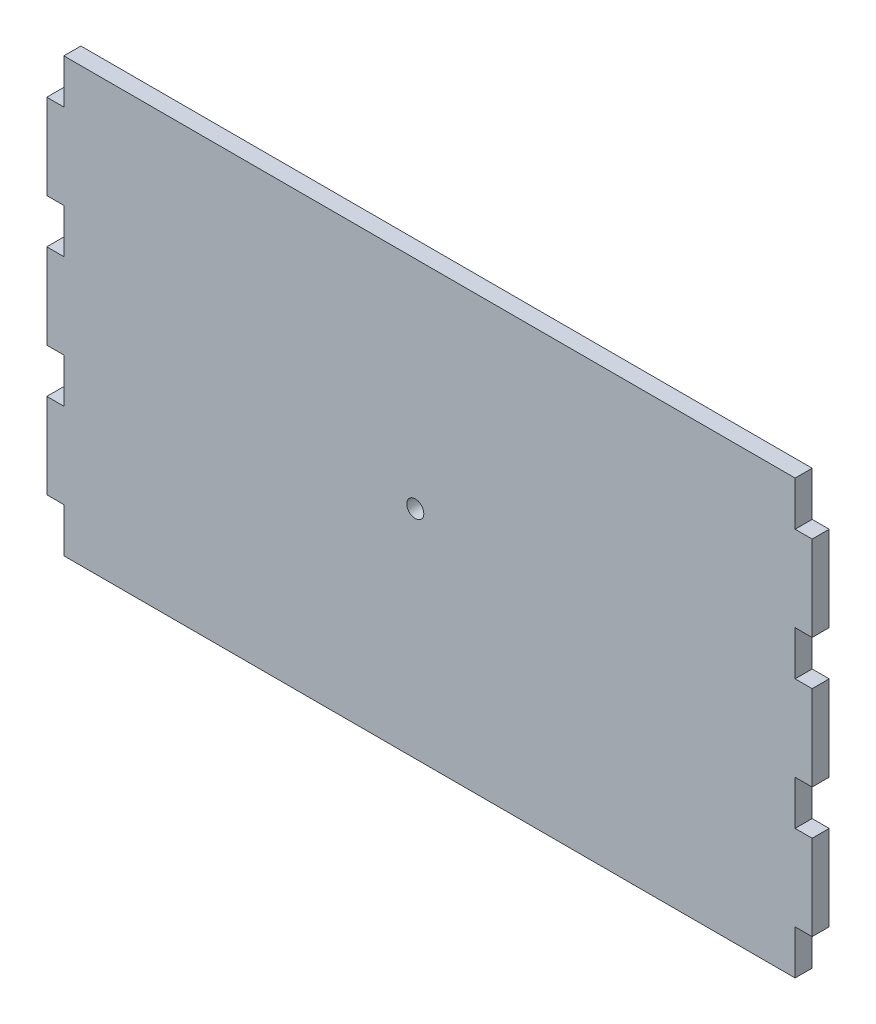
SolidWorks part; units mm, degrees
material "ENPH 253 Hardboard"
ref_plane "Front Plane" through (0, 0, 0) normal (0, 0, 1) x (1, 0, 0)
ref_plane "Top Plane" through (0, 0, 0) normal (0, 1, 0) x (1, 0, 0)
ref_plane "Right Plane" through (0, 0, 0) normal (1, 0, 0) x (0, 0, -1)
sketch "Sketch1" plane through (0, 0, 0) normal (0, 0, 1) x (1, 0, 0)
  line L1 (-67.35, 38.1) -> (67.35, 38.1)
  line L2 (-67.35, 38.1) -> (-67.35, -38.1)
  line L3 (-67.35, -38.1) -> (67.35, -38.1)
  line L4 (67.35, 38.1) -> (67.35, -38.1)
  line L5 (-67.35, 38.1) -> (67.35, -38.1) construction
  line L6 (-67.35, -38.1) -> (67.35, 38.1) construction
  point P0 (0, 0)
  dimension "D1" = 134.7
  dimension "D2" = 76.2
extrude "Boss-Extrude1" add sketch "Sketch1" along normal blind 3
sketch "Sketch2" plane through (0, 0, 3) normal (0, 0, 1) x (1, 0, 0)
  line L1 (-67.35, 38.1) -> (-64.35, 38.1)
  line L2 (-67.35, 38.1) -> (-67.35, 30.3)
  line L3 (-67.35, 30.3) -> (-64.35, 30.3)
  line L4 (-64.35, 38.1) -> (-64.35, 30.3)
  dimension "D1" = 3
  dimension "D2" = 7.8
extrude "Cut-Extrude1" cut sketch "Sketch2" against normal through all
pattern_linear "LPattern1" count 4 spacing 22.8 along (0, -1, 0) of "Cut-Extrude1"
hole_wizard "Ø3.0mm Clearance Dowel Hole1" positions "Sketch3" profile "Sketch4" hole size "Ø3.0" standard "ANSI Metric" end condition through all
sketch "Sketch3" plane through (0, 0, 3) normal (0, 0, 1) x (1, 0, 0)
  line L0 (-67.35, 7.5) -> (-67.35, -7.5) construction
  point P0 (-2.5, 0)
  point P11 (0, 0)
  point P12 (0, 0)
  point P13 (0, 0)
  point P14 (0, 0)
  point P15 (0, 0)
  point P16 (0, 0)
  dimension "D1" = 64.85
sketch "Sketch4" plane through (-2.5, 0, 3) normal (1, 0, 0) x (0, -1, 0)
  line L0 (0, 0) -> (0, 3)
  line L1 (0, 3) -> (1.5, 3)
  line L2 (1.5, 3) -> (1.5, 0)
  line L5 (1.5, 0) -> (0, 0)
  line L11 (0, -6.35) -> (0, 107.95) construction
  dimension "Thru Hole Dia." = 3
  dimension "Thru Hole Depth" = 3
mirror "Mirror4" about plane through (0, 0, 0) normal (1, 0, 0) of "LPattern1"
